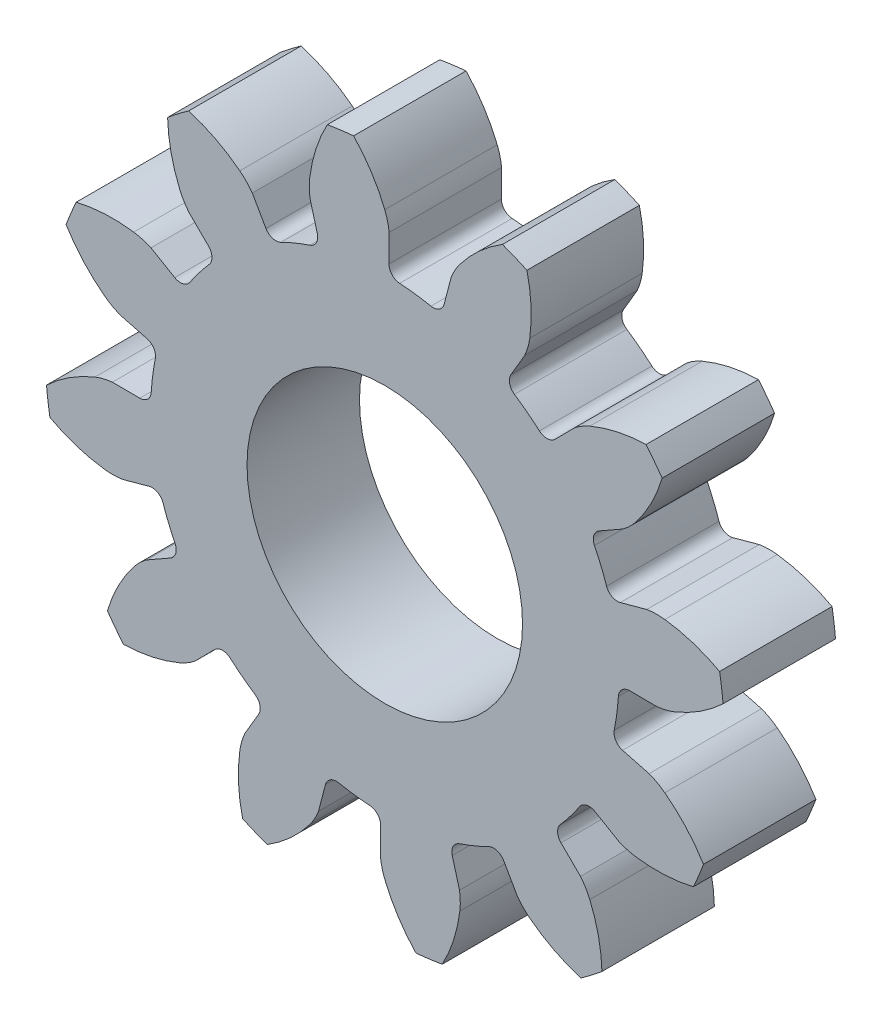
SolidWorks part; units mm, degrees
ref_plane "Front Plane" through (0, 0, 0) normal (0, 0, 1) x (1, 0, 0)
ref_plane "Top Plane" through (0, 0, 0) normal (0, 1, 0) x (1, 0, 0)
ref_plane "Right Plane" through (0, 0, 0) normal (1, 0, 0) x (0, 0, -1)
sketch "Sketch1" plane through (0, 0, 0) normal (0, 0, 1) x (1, 0, 0)
  line L48 (-1.3289, 4.6605) -> (-1.1999, 4.1898)
  line L49 (-2.1142, 3.8111) -> (-2.3558, 4.2352)
  line L50 (-3.4812, 3.3716) -> (-3.134, 3.0285)
  line L51 (-3.7365, 2.2434) -> (-4.1577, 2.4899)
  line L52 (-4.7006, 1.1794) -> (-4.2284, 1.0558)
  line L53 (-4.3576, 0.0746) -> (-4.8457, 0.0774)
  line L54 (-4.6605, -1.3289) -> (-4.1898, -1.1999)
  line L55 (-3.8111, -2.1142) -> (-4.2352, -2.3558)
  line L56 (-3.3716, -3.4812) -> (-3.0285, -3.134)
  line L57 (-2.2434, -3.7365) -> (-2.4899, -4.1577)
  line L58 (-1.1794, -4.7006) -> (-1.0558, -4.2284)
  line L59 (-0.0746, -4.3576) -> (-0.0774, -4.8457)
  line L60 (1.3289, -4.6605) -> (1.1999, -4.1898)
  line L61 (2.1142, -3.8111) -> (2.3558, -4.2352)
  line L62 (3.4812, -3.3716) -> (3.134, -3.0285)
  line L63 (3.7365, -2.2434) -> (4.1577, -2.4899)
  line L64 (4.7006, -1.1794) -> (4.2284, -1.0558)
  line L65 (4.3576, -0.0746) -> (4.8457, -0.0774)
  line L66 (4.6605, 1.3289) -> (4.1898, 1.1999)
  line L67 (3.8111, 2.1142) -> (4.2352, 2.3558)
  line L68 (3.3716, 3.4812) -> (3.0285, 3.134)
  line L69 (2.2434, 3.7365) -> (2.4899, 4.1577)
  line L70 (1.1794, 4.7006) -> (1.0558, 4.2284)
  line L71 (0.0746, 4.3576) -> (0.0774, 4.8457)
  circle A0 centre (0, 0) radius 2.45
  arc A192 (0.0002, 5.1569) -> (-0.5543, 6.0169) centre (-2.5558, 4.1176) ccw
  arc A193 (-0.5543, 6.0169) -> (-1.0218, 5.9553) centre (0, 0) ccw
  arc A194 (-1.0218, 5.9553) -> (-1.3349, 4.9811) centre (1.403, 4.6388) ccw
  arc A195 (-1.3349, 4.9811) -> (-1.3289, 4.6605) centre (-0.2176, 4.8414) ccw
  arc A196 (-1.3304, 3.9445) -> (-1.1999, 4.1898) centre (-1.3951, 4.1363) ccw
  arc A197 (-1.3304, 3.9445) -> (-1.8484, 3.7299) centre (0, 0) ccw
  arc A198 (-2.1142, 3.8111) -> (-1.8484, 3.7299) centre (-1.9383, 3.9113) ccw
  arc A199 (-2.3558, 4.2352) -> (-2.5783, 4.4661) centre (-3.2695, 3.5772) ccw
  arc A200 (-2.5783, 4.4661) -> (-3.4885, 4.9336) centre (-4.2721, 2.288) ccw
  arc A201 (-3.4885, 4.9336) -> (-3.8626, 4.6465) centre (0, 0) ccw
  arc A202 (-3.8626, 4.6465) -> (-3.6466, 3.6463) centre (-1.1044, 4.7188) ccw
  arc A203 (-3.6466, 3.6463) -> (-3.4812, 3.3716) centre (-2.6091, 4.084) ccw
  arc A204 (-3.1244, 2.7508) -> (-3.134, 3.0285) centre (-3.2763, 2.8846) ccw
  arc A205 (-3.1244, 2.7508) -> (-3.4657, 2.306) centre (0, 0) ccw
  arc A206 (-3.7365, 2.2434) -> (-3.4657, 2.306) centre (-3.6343, 2.4181) ccw
  arc A207 (-4.1577, 2.4899) -> (-4.4659, 2.5786) centre (-4.6201, 1.4632) ccw
  arc A208 (-4.4659, 2.5786) -> (-5.4879, 2.5284) centre (-4.8438, -0.1546) ccw
  arc A209 (-5.4879, 2.5284) -> (-5.6684, 2.0927) centre (0, 0) ccw
  arc A210 (-5.6684, 2.0927) -> (-4.9812, 1.3345) centre (-3.3158, 3.5344) ccw
  arc A211 (-4.9812, 1.3345) -> (-4.7006, 1.1794) centre (-4.3015, 2.2323) ccw
  arc A212 (-4.0812, 0.8201) -> (-4.2284, 1.0558) centre (-4.2797, 0.86) ccw
  arc A213 (-4.0812, 0.8201) -> (-4.1544, 0.2642) centre (0, 0) ccw
  arc A214 (-4.3576, 0.0746) -> (-4.1544, 0.2642) centre (-4.3564, 0.277) ccw
  arc A215 (-4.8457, 0.0774) -> (-5.1569, 0.0002) centre (-4.7327, -1.0429) ccw
  arc A216 (-5.1569, 0.0002) -> (-6.0169, -0.5543) centre (-4.1176, -2.5558) ccw
  arc A217 (-6.0169, -0.5543) -> (-5.9553, -1.0218) centre (0, 0) ccw
  arc A218 (-5.9553, -1.0218) -> (-4.9811, -1.3349) centre (-4.6388, 1.403) ccw
  arc A219 (-4.9811, -1.3349) -> (-4.6605, -1.3289) centre (-4.8414, -0.2176) ccw
  arc A220 (-3.9445, -1.3304) -> (-4.1898, -1.1999) centre (-4.1363, -1.3951) ccw
  arc A221 (-3.9445, -1.3304) -> (-3.7299, -1.8484) centre (0, 0) ccw
  arc A222 (-3.8111, -2.1142) -> (-3.7299, -1.8484) centre (-3.9113, -1.9383) ccw
  arc A223 (-4.2352, -2.3558) -> (-4.4661, -2.5783) centre (-3.5772, -3.2695) ccw
  arc A224 (-4.4661, -2.5783) -> (-4.9336, -3.4885) centre (-2.288, -4.2721) ccw
  arc A225 (-4.9336, -3.4885) -> (-4.6465, -3.8626) centre (0, 0) ccw
  arc A226 (-4.6465, -3.8626) -> (-3.6463, -3.6466) centre (-4.7188, -1.1044) ccw
  arc A227 (-3.6463, -3.6466) -> (-3.3716, -3.4812) centre (-4.084, -2.6091) ccw
  arc A228 (-2.7508, -3.1244) -> (-3.0285, -3.134) centre (-2.8846, -3.2763) ccw
  arc A229 (-2.7508, -3.1244) -> (-2.306, -3.4657) centre (0, 0) ccw
  arc A230 (-2.2434, -3.7365) -> (-2.306, -3.4657) centre (-2.4181, -3.6343) ccw
  arc A231 (-2.4899, -4.1577) -> (-2.5786, -4.4659) centre (-1.4632, -4.6201) ccw
  arc A232 (-2.5786, -4.4659) -> (-2.5284, -5.4879) centre (0.1546, -4.8438) ccw
  arc A233 (-2.5284, -5.4879) -> (-2.0927, -5.6684) centre (0, 0) ccw
  arc A234 (-2.0927, -5.6684) -> (-1.3345, -4.9812) centre (-3.5344, -3.3158) ccw
  arc A235 (-1.3345, -4.9812) -> (-1.1794, -4.7006) centre (-2.2323, -4.3015) ccw
  arc A236 (-0.8201, -4.0812) -> (-1.0558, -4.2284) centre (-0.86, -4.2797) ccw
  arc A237 (-0.8201, -4.0812) -> (-0.2642, -4.1544) centre (0, 0) ccw
  arc A238 (-0.0746, -4.3576) -> (-0.2642, -4.1544) centre (-0.277, -4.3564) ccw
  arc A239 (-0.0774, -4.8457) -> (-0.0002, -5.1569) centre (1.0429, -4.7327) ccw
  arc A240 (-0.0002, -5.1569) -> (0.5543, -6.0169) centre (2.5558, -4.1176) ccw
  arc A241 (0.5543, -6.0169) -> (1.0218, -5.9553) centre (0, 0) ccw
  arc A242 (1.0218, -5.9553) -> (1.3349, -4.9811) centre (-1.403, -4.6388) ccw
  arc A243 (1.3349, -4.9811) -> (1.3289, -4.6605) centre (0.2176, -4.8414) ccw
  arc A244 (1.3304, -3.9445) -> (1.1999, -4.1898) centre (1.3951, -4.1363) ccw
  arc A245 (1.3304, -3.9445) -> (1.8484, -3.7299) centre (0, 0) ccw
  arc A246 (2.1142, -3.8111) -> (1.8484, -3.7299) centre (1.9383, -3.9113) ccw
  arc A247 (2.3558, -4.2352) -> (2.5783, -4.4661) centre (3.2695, -3.5772) ccw
  arc A248 (2.5783, -4.4661) -> (3.4885, -4.9336) centre (4.2721, -2.288) ccw
  arc A249 (3.4885, -4.9336) -> (3.8626, -4.6465) centre (0, 0) ccw
  arc A250 (3.8626, -4.6465) -> (3.6466, -3.6463) centre (1.1044, -4.7188) ccw
  arc A251 (3.6466, -3.6463) -> (3.4812, -3.3716) centre (2.6091, -4.084) ccw
  arc A252 (3.1244, -2.7508) -> (3.134, -3.0285) centre (3.2763, -2.8846) ccw
  arc A253 (3.1244, -2.7508) -> (3.4657, -2.306) centre (0, 0) ccw
  arc A254 (3.7365, -2.2434) -> (3.4657, -2.306) centre (3.6343, -2.4181) ccw
  arc A255 (4.1577, -2.4899) -> (4.4659, -2.5786) centre (4.6201, -1.4632) ccw
  arc A256 (4.4659, -2.5786) -> (5.4879, -2.5284) centre (4.8438, 0.1546) ccw
  arc A257 (5.4879, -2.5284) -> (5.6684, -2.0927) centre (0, 0) ccw
  arc A258 (5.6684, -2.0927) -> (4.9812, -1.3345) centre (3.3158, -3.5344) ccw
  arc A259 (4.9812, -1.3345) -> (4.7006, -1.1794) centre (4.3015, -2.2323) ccw
  arc A260 (4.0812, -0.8201) -> (4.2284, -1.0558) centre (4.2797, -0.86) ccw
  arc A261 (4.0812, -0.8201) -> (4.1544, -0.2642) centre (0, 0) ccw
  arc A262 (4.3576, -0.0746) -> (4.1544, -0.2642) centre (4.3564, -0.277) ccw
  arc A263 (4.8457, -0.0774) -> (5.1569, -0.0002) centre (4.7327, 1.0429) ccw
  arc A264 (5.1569, -0.0002) -> (6.0169, 0.5543) centre (4.1176, 2.5558) ccw
  arc A265 (6.0169, 0.5543) -> (5.9553, 1.0218) centre (0, 0) ccw
  arc A266 (5.9553, 1.0218) -> (4.9811, 1.3349) centre (4.6388, -1.403) ccw
  arc A267 (4.9811, 1.3349) -> (4.6605, 1.3289) centre (4.8414, 0.2176) ccw
  arc A268 (3.9445, 1.3304) -> (4.1898, 1.1999) centre (4.1363, 1.3951) ccw
  arc A269 (3.9445, 1.3304) -> (3.7299, 1.8484) centre (0, 0) ccw
  arc A270 (3.8111, 2.1142) -> (3.7299, 1.8484) centre (3.9113, 1.9383) ccw
  arc A271 (4.2352, 2.3558) -> (4.4661, 2.5783) centre (3.5772, 3.2695) ccw
  arc A272 (4.4661, 2.5783) -> (4.9336, 3.4885) centre (2.288, 4.2721) ccw
  arc A273 (4.9336, 3.4885) -> (4.6465, 3.8626) centre (0, 0) ccw
  arc A274 (4.6465, 3.8626) -> (3.6463, 3.6466) centre (4.7188, 1.1044) ccw
  arc A275 (3.6463, 3.6466) -> (3.3716, 3.4812) centre (4.084, 2.6091) ccw
  arc A276 (2.7508, 3.1244) -> (3.0285, 3.134) centre (2.8846, 3.2763) ccw
  arc A277 (2.7508, 3.1244) -> (2.306, 3.4657) centre (0, 0) ccw
  arc A278 (2.2434, 3.7365) -> (2.306, 3.4657) centre (2.4181, 3.6343) ccw
  arc A279 (2.4899, 4.1577) -> (2.5786, 4.4659) centre (1.4632, 4.6201) ccw
  arc A280 (2.5786, 4.4659) -> (2.5284, 5.4879) centre (-0.1546, 4.8438) ccw
  arc A281 (2.5284, 5.4879) -> (2.0927, 5.6684) centre (0, 0) ccw
  arc A282 (2.0927, 5.6684) -> (1.3345, 4.9812) centre (3.5344, 3.3158) ccw
  arc A283 (1.3345, 4.9812) -> (1.1794, 4.7006) centre (2.2323, 4.3015) ccw
  arc A284 (0.8201, 4.0812) -> (1.0558, 4.2284) centre (0.86, 4.2797) ccw
  arc A285 (0.8201, 4.0812) -> (0.2642, 4.1544) centre (0, 0) ccw
  arc A286 (0.0746, 4.3576) -> (0.2642, 4.1544) centre (0.277, 4.3564) ccw
  arc A287 (0.0774, 4.8457) -> (0.0002, 5.1569) centre (-1.0429, 4.7327) ccw
  dimension "D1" = 4.9
extrude "Boss-Extrude1" add sketch "Sketch1" along normal blind 2
